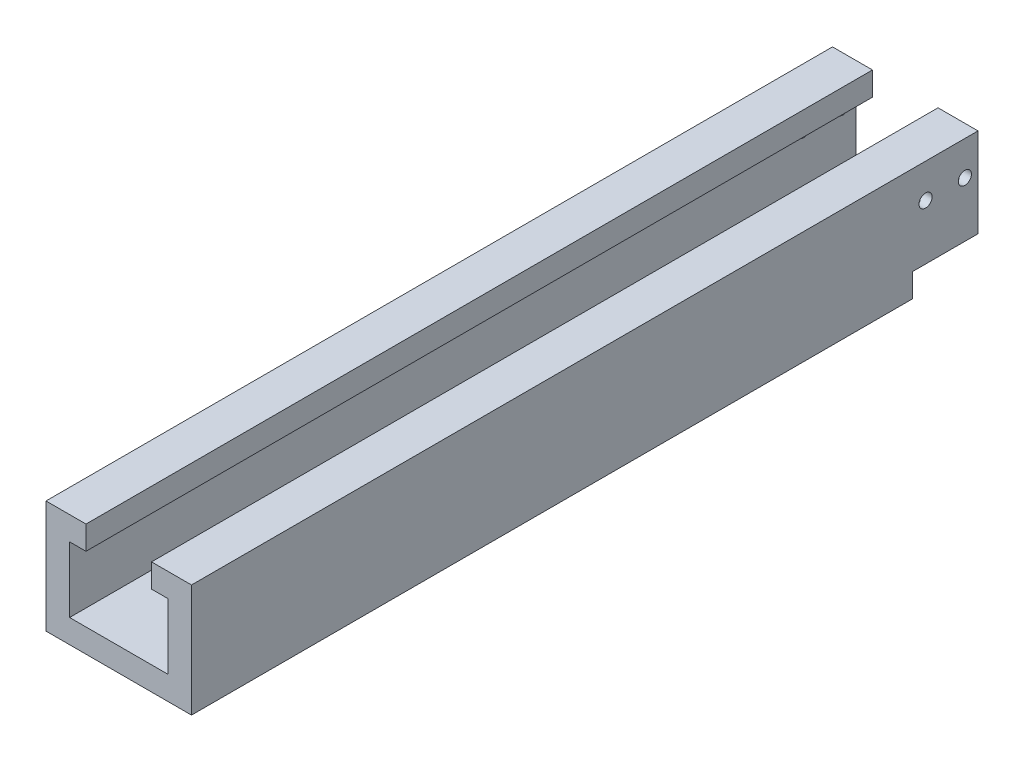
SolidWorks part; units mm, degrees
material "Beech"
ref_plane "Front Plane" through (0, 0, 0) normal (0, 0, 1) x (1, 0, 0)
ref_plane "Top Plane" through (0, 0, 0) normal (0, 1, 0) x (1, 0, 0)
ref_plane "Right Plane" through (0, 0, 0) normal (1, 0, 0) x (0, 0, -1)
sketch "Sketch1" plane through (0, 0, 0) normal (0, 0, 1) x (1, 0, 0)
  line L1 (0, 0) -> (111, 0)
  line L2 (0, 0) -> (0, 18)
  line L3 (0, 18) -> (111, 18)
  line L4 (111, 0) -> (111, 18)
  dimension "D1" = 18
  dimension "D2" = 111
extrude "baseplate" add sketch "Sketch1" along normal blind 600
sketch "Sketch2" plane through (0, 18, 0) normal (0, 1, 0) x (1, 0, 0)
  line L0 (111, -600) -> (0, -600) construction
  line L1 (0, 0) -> (18, 0)
  line L2 (0, 0) -> (0, -600)
  line L3 (0, -600) -> (18, -600)
  line L4 (18, 0) -> (18, -600)
  dimension "D1" = 18
extrude "side_rail" add sketch "Sketch2" along normal blind 50
sketch "Sketch3" plane through (0, 68, 0) normal (0, 1, 0) x (1, 0, 0)
  line L0 (111, -600) -> (18, -600) construction
  line L1 (0, 0) -> (30.5, 0)
  line L2 (0, 0) -> (0, -600)
  line L3 (0, -600) -> (30.5, -600)
  line L4 (30.5, 0) -> (30.5, -600)
  dimension "D1" = 30.5
extrude "keeper rail" add sketch "Sketch3" along normal blind 18
ref_plane "longitudinal midplane" through (55.5, 0, 0) normal (-1, 0, 0) x (0, 0, 1)
mirror "mirror rails" about plane through (55.5, 0, 0) normal (-1, 0, 0) of "keeper rail", "side_rail"
sketch "Sketch5" plane through (0, 0, 0) normal (0, -1, 0) x (1, 0, 0)
  line L0 (111, 600) -> (111, 0) construction
  line L1 (0, 0) -> (111, 0)
  line L2 (0, 0) -> (0, 50)
  line L3 (0, 50) -> (111, 50)
  line L4 (111, 0) -> (111, 50)
  dimension "D1" = 50
extrude "lap joint cutout" cut sketch "Sketch5" against normal blind 18
hole_wizard "lap joint bolt hole pattern" positions "Sketch7" profile "Sketch9" hole size "M6" standard "ANSI Metric"
sketch "Sketch7" plane through (0, 18, 0) normal (0, -1, 0) x (-1, 0, 0)
  line L1 (-102, -10) -> (-9, -10)
  line L2 (-102, -10) -> (-102, -40)
  line L3 (-102, -40) -> (-9, -40)
  line L4 (-9, -10) -> (-9, -40)
  line L5 (-102, 0) -> (-102, -10)
  line L6 (-93, 0) -> (-111, 0) construction
  line L8 (-9, -10) -> (-9, 0)
  line L9 (0, 0) -> (-18, 0) construction
  line L10 (-9, -25) -> (0, -25)
  line L11 (0, -50) -> (0, 0) construction
  point P1 (-102, -10)
  point P2 (-9, -40)
  point P113 (-102, -40)
  point P114 (-9, -10)
sketch "Sketch9" plane through (102, 18, 10) normal (1, 0, 0) x (0, 0, -1)
  line L0 (0, 0) -> (0, 58.9828)
  line L1 (0, 58.9828) -> (3.3, 57)
  line L2 (3.3, 57) -> (3.3, 0)
  line L5 (3.3, 0) -> (0, 0)
  line L10 (0, 58.9828) -> (-3.3, 57) construction
  line L11 (0, -6.35) -> (0, 107.95) construction
  dimension "Hole Dia." = 6.6
  dimension "Hole Depth" = 57
  dimension "Drill Angle" = 118
hole_wizard "fixed bearing block bolt clearance holes" positions "Sketch10" profile "Sketch11" hole size "M6" standard "ANSI Metric" end condition through all
sketch "Sketch10" plane through (0, 18, 0) normal (0, 1, 0) x (1, 0, 0)
  line L0 (37.5, -535) -> (73.5, -535)
  line L2 (55.5, -535) -> (55.5, -600)
  line L3 (93, -600) -> (18, -600) construction
  point P0 (37.5, -535)
  point P2 (73.5, -535)
  dimension "D1" = 36
  dimension "D2" = 65
sketch "Sketch11" plane through (37.5, 18, 535) normal (1, 0, 0) x (0, 0, 1)
  line L0 (0, 0) -> (0, 18)
  line L1 (0, 18) -> (3.3, 18)
  line L2 (3.3, 18) -> (3.3, 0)
  line L5 (3.3, 0) -> (0, 0)
  line L11 (0, -6.35) -> (0, 107.95) construction
  dimension "Thru Hole Dia." = 6.6
  dimension "Thru Hole Depth" = 18
ref_axis "bottom foot bolt hole axis" through (102, 81.8786, 10) along (0, -1, 0)
ref_axis "top foot bolt hole axis" through (102, 75, 40) along (0, -1, 0)
hole_wizard "cross dowel bolt clearance holes" positions "Sketch14" profile "Sketch15" hole size "Ø10.0" standard "ANSI Metric" end condition through all
sketch "Sketch14" plane through (111, 0, 0) normal (1, 0, 0) x (0, 0, -1)
  line L0 (-40, 75) -> (-40, 18) construction
  line L1 (-10, 81.8786) -> (-10, 18) construction
  line L2 (-40, 60) -> (-10, 60)
  line L4 (-36.7, 75) -> (-43.3, 75) construction
  line L5 (-6.7, 75) -> (-13.3, 75) construction
  line L6 (-36.7, 75) -> (-43.3, 75)
  line L7 (-6.7, 75) -> (-13.3, 75)
  point P0 (-40, 60)
  point P4 (-10, 60)
  dimension "D1" = 15
sketch "Sketch15" plane through (111, 60, 40) normal (0, 1, 0) x (0, 0, -1)
  line L0 (0, 0) -> (0, 111)
  line L1 (0, 111) -> (5, 111)
  line L2 (5, 111) -> (5, 0)
  line L5 (5, 0) -> (0, 0)
  line L11 (0, -6.35) -> (0, 107.95) construction
  dimension "Thru Hole Dia." = 10
  dimension "Thru Hole Depth" = 111
equation "\"board_thickness\"= 18mm"
equation "\"way_width\"= 75mm"
equation "\"way_thickness\"= 50mm"
equation "\"radial_clearance\"= 0.1mm"
equation "\"slider_width\"= \"way_width\"-2* \"radial_clearance\" - 2*0.65"
equation "\"slider_thickness\"= \"way_thickness\" - 2 * \"radial_clearance\""
equation "\"column_width\"= \"way_width\" + 2 * \"board_thickness\""
equation "\"D1@Sketch1\"=\"board_thickness\""
equation "\"D2@Sketch1\"=\"column_width\""
equation "\"D1@Sketch2\"=\"board_thickness\""
equation "\"D1@keeper rail\"=\"board_thickness\""
equation "\"boxway_slot_width\"= 50mm"
equation "\"keeper_rail_width\"= (\"column_width\" - \"boxway_slot_width\")/2"
equation "\"D1@Sketch3\"=\"keeper_rail_width\""
equation "\"slider_length\"= 125mm"
equation "\"nut_diameter\"= 22mm"
equation "\"nut_length\"= 15mm"
equation "\"leadscrew_diameter\"= 10mm"
equation "\"leadscrew_radial_clearance\"= 1mm"
equation "\"bearing_bolt_pattern_width\"= 30mm"
equation "\"bearing_bolt_pattern_height\"= 75mm"
equation "\"desktop_bolt_pattern_width\"= 30mm"
equation "\"desktop_bolt_pattern_height\"= 30mm"
equation "\"bearing_bolt_nut_counterbore_diameter\"= 12mm"
equation "\"bearing_bolt_nut_counterbore_depth\"= 10mm"
equation "\"desktop_depth\"= 500mm"
equation "\"desktop_width\"= 650mm"
equation "\"desktop_thickness\"= 18mm"
equation "\"leg_height\"=100mm"
equation "\"leg_width\"=18mm"
equation "\"leg_length\"=500mm"
equation "\"D1@lap joint cutout\" = \"leg_width\""
equation "\"lap_joint_height\"= 50mm"
equation "\"lap_dowel_diameter\"= 8mm"
equation "\"lap_dowel_hole_z_spacing\"=30"
equation "\"D1@Sketch5\"=\"lap_joint_height\""
equation "\"D1@Sketch7\"=\"lap_dowel_hole_z_spacing\""
